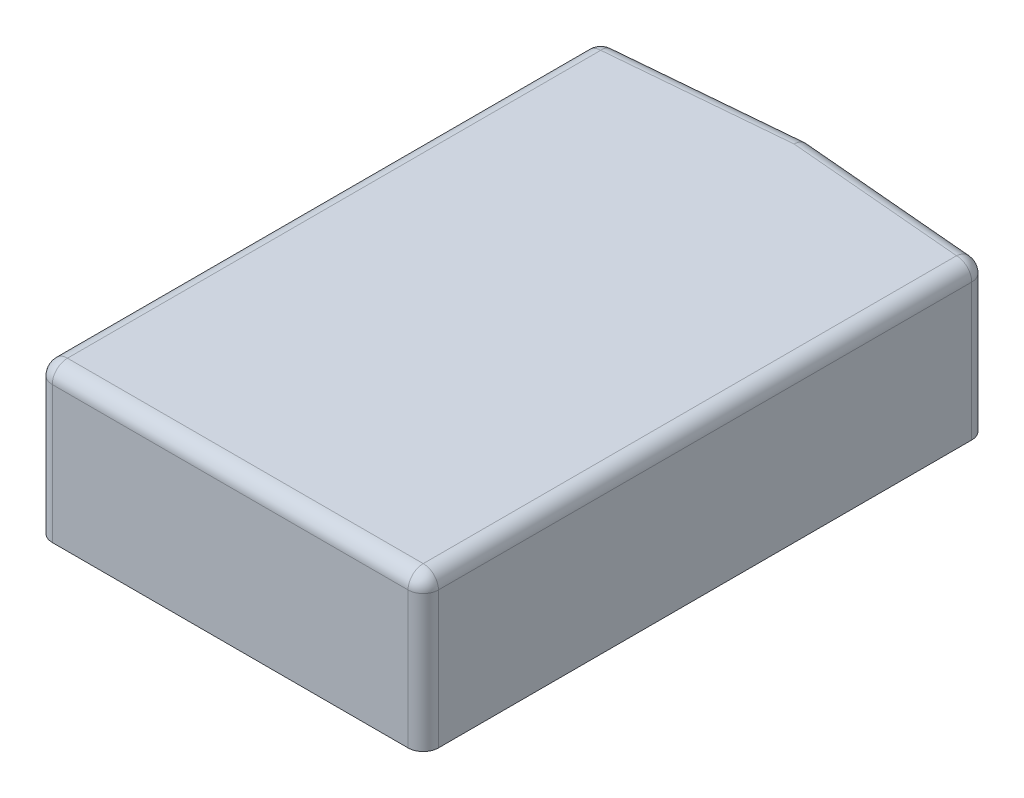
SolidWorks part; units mm, degrees
ref_plane "Front Plane" through (0, 0, 0) normal (0, 0, 1) x (1, 0, 0)
ref_plane "Top Plane" through (0, 0, 0) normal (0, 1, 0) x (1, 0, 0)
ref_plane "Right Plane" through (0, 0, 0) normal (1, 0, 0) x (0, 0, -1)
sketch "Sketch1" plane through (0, 0, 0) normal (0, 1, 0) x (1, 0, 0)
  line L1 (-25.4, -38.1) -> (25.4, -38.1)
  line L2 (-25.4, -38.1) -> (-25.4, 38.1)
  line L3 (-25.4, 38.1) -> (25.4, 38.1)
  line L4 (25.4, -38.1) -> (25.4, 38.1)
  line L5 (-25.4, -38.1) -> (25.4, 38.1) construction
  line L6 (-25.4, 38.1) -> (25.4, -38.1) construction
  point P0 (0, 0)
  dimension "D1" = 50.8
  dimension "D2" = 76.2
extrude "Boss-Extrude2" add sketch "Sketch1" along normal blind 20 contours L3 L4 L1 L2
sketch "Sketch2" plane through (0, 0, -38.1) normal (0, 0, -1) x (-1, 0, 0)
  line L0 (-25.4, 20) -> (-25.4, 0) construction
  line L1 (25.4, 20) -> (25.4, 0) construction
  line L2 (25.4, 20) -> (-25.4, 20) construction
  circle A0 centre (-15.4, 10) radius 3.7
  circle A1 centre (15.4, 10) radius 3.7
  dimension "D1" = 10
  dimension "D2" = 10
  dimension "D3" = 10
  dimension "D4" = 10
extrude "Boss-Extrude3" add sketch "Sketch2" along normal blind 2
chamfer "Chamfer7" distance 25.4 angle 5 2 edges at (-25.4, 10, -38.1) (25.4, 10, -38.1) first distance on face at (-19.1, 10, -38.1)
fillet "Fillet6" radius 2 5 edges at (25.4, 20, 1.1111) (0, 20, 38.1) (-25.4, 20, 1.1111) (-12.7, 20, -36.9889) (12.7, 20, -36.9889)
fillet "Fillet7" radius 2 2 edges at (24.8142, 19.4142, -35.341) (25.4, 9, -35.8778)
fillet "Fillet8" radius 2 2 edges at (24.8142, 19.4142, 37.5142) (25.4, 9, 38.1)
fillet "Fillet9" radius 2 2 edges at (-24.8142, 19.4142, 37.5142) (-25.4, 9, 38.1)
fillet "Fillet10" radius 2 2 edges at (-24.8142, 19.4142, -35.341) (-25.4, 9, -35.8778)
sketch "Sketch3" plane through (0, 20, 0) normal (0, 1, 0) x (1, 0, 0)
  line L1 (11.8216, 26.662) -> (-5.619, 26.662)
  line L2 (11.8216, 26.662) -> (11.8216, -26.3221)
  line L3 (11.8216, -26.3221) -> (-5.619, -26.3221)
  line L4 (-5.619, 26.662) -> (-5.619, -26.3221)
  text T0 "ALFA AWUS036ACH\r\nWifi Downlink"
